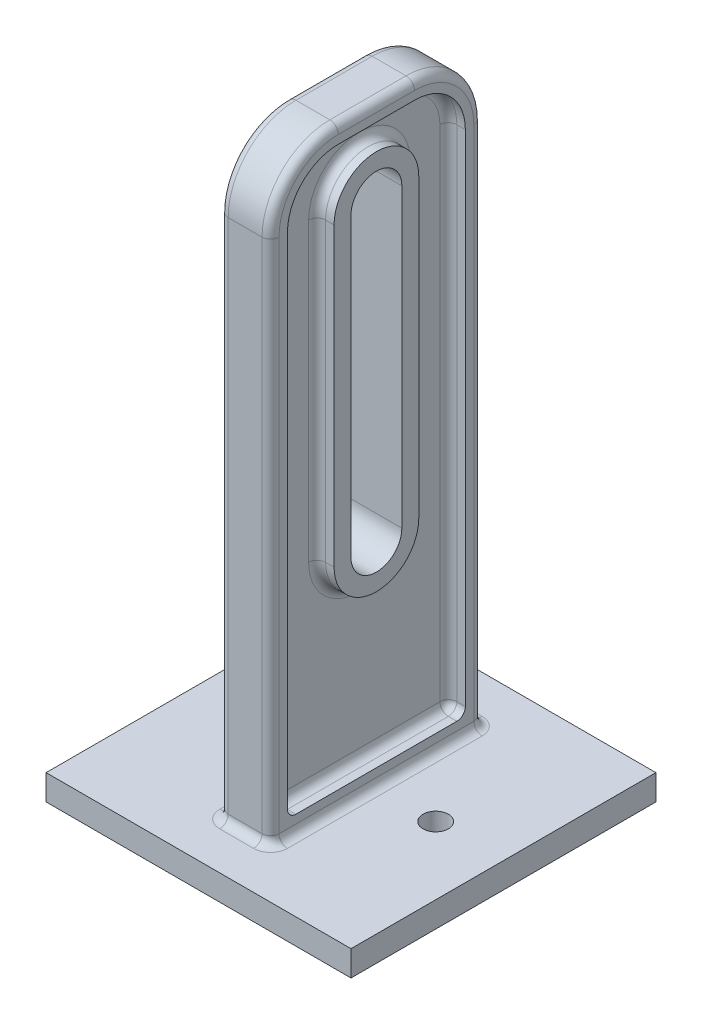
SolidWorks part; units mm, degrees
ref_plane "Front Plane" through (0, 0, 0) normal (0, 0, 1) x (1, 0, 0)
ref_plane "Top Plane" through (0, 0, 0) normal (0, 1, 0) x (1, 0, 0)
ref_plane "Right Plane" through (0, 0, 0) normal (1, 0, 0) x (0, 0, -1)
sketch "Sketch1" plane through (0, 0, 0) normal (0, 1, 0) x (1, 0, 0)
  line L1 (-18, -18) -> (18, -18)
  line L2 (-18, -18) -> (-18, 18)
  line L3 (-18, 18) -> (18, 18)
  line L4 (18, -18) -> (18, 18)
  line L5 (-18, -18) -> (18, 18) construction
  line L6 (-18, 18) -> (18, -18) construction
  point P0 (0, 0)
  dimension "D1" = 36
  dimension "D2" = 36
extrude "Boss-Extrude1" add sketch "Sketch1" along normal blind 3
sketch "Sketch2" plane through (0, 3, 0) normal (0, 1, 0) x (1, 0, 0)
  line L0 (0, 0) -> (0, 8.7395) construction
  line L1 (0, 0) -> (10, 0) construction
  circle A0 centre (-10, 0) radius 1.5
  circle A1 centre (10, 0) radius 1.5
  dimension "D2" = 3
  dimension "D1" = 20
extrude "Cut-Extrude1" cut sketch "Sketch2" against normal blind 3
sketch "Sketch3" plane through (0, 3, 0) normal (0, 1, 0) x (1, 0, 0)
  line L1 (-3, 12.5) -> (3, 12.5)
  line L2 (-3, 12.5) -> (-3, -12.5)
  line L3 (-3, -12.5) -> (3, -12.5)
  line L4 (3, 12.5) -> (3, -12.5)
  line L5 (-3, 12.5) -> (3, -12.5) construction
  line L6 (-3, -12.5) -> (3, 12.5) construction
  point P0 (0, 0)
  dimension "D1" = 25
  dimension "D2" = 6
extrude "Boss-Extrude2" add sketch "Sketch3" along normal blind 70
sketch "Sketch4" plane through (3, 0, 0) normal (1, 0, 0) x (0, 0, -1)
  line L0 (-12.5, 73) -> (12.5, 73) construction
  line L3 (-8.3079, 45.5) -> (10.2679, 45.5) construction
  line L4 (0, 0) -> (0, 52.2737) construction
  line L5 (0, 63) -> (0, 28) construction
  line L6 (3, 63) -> (3, 28)
  line L7 (-3, 63) -> (-3, 28)
  arc A2 (3, 63) -> (-3, 63) centre (0, 63) ccw
  arc A3 (-3, 28) -> (3, 28) centre (0, 28) ccw
  point P8 (0, 45.5)
  dimension "D2" = 3
  dimension "D3" = 35
  dimension "D1" = 10
extrude "Cut-Extrude2" cut sketch "Sketch4" against normal blind 70
fillet "Fillet1" radius 8 1 edges at (0, 73, 12.5)
fillet "Fillet2" radius 8 1 edges at (0, 73, -12.5)
sketch "Sketch5" plane through (3, 0, 0) normal (1, 0, 0) x (0, 0, -1)
  line L66 (-10.5, 5) -> (10.5, 5)
  line L67 (-10.5, 65) -> (-10.5, 5)
  line L68 (10.5, 5) -> (10.5, 65)
  line L69 (4.5, 71) -> (-4.5, 71)
  line L70 (-10.5, 5) -> (10.5, 5)
  line L71 (-10.5, 65) -> (-10.5, 5)
  line L72 (10.5, 5) -> (10.5, 65)
  line L73 (4.5, 71) -> (-4.5, 71)
  line L78 (5, 28) -> (5, 63)
  line L79 (-5, 63) -> (-5, 28)
  line L80 (5, 28) -> (5, 63)
  line L81 (-5, 63) -> (-5, 28)
  arc A44 (10.5, 65) -> (4.5, 71) centre (4.5, 65) ccw
  arc A45 (-4.5, 71) -> (-10.5, 65) centre (-4.5, 65) ccw
  arc A46 (10.5, 65) -> (4.5, 71) centre (4.5, 65) ccw
  arc A47 (-4.5, 71) -> (-10.5, 65) centre (-4.5, 65) ccw
  arc A52 (-5, 28) -> (5, 28) centre (0, 28) ccw
  arc A53 (5, 63) -> (-5, 63) centre (0, 63) ccw
  arc A54 (-5, 28) -> (5, 28) centre (0, 28) ccw
  arc A55 (5, 63) -> (-5, 63) centre (0, 63) ccw
  dimension "D1" = 2
  dimension "D2" = 2
extrude "Cut-Extrude3" cut sketch "Sketch5" against normal blind 2
mirror "Mirror1" about plane through (0, 0, 0) normal (1, 0, 0) of "Cut-Extrude3"
fillet "Fillet3" radius 1 4 edges at (1, 45.5, 5) (1, 68, 0) (1, 23, 0) (1, 45.5, -5)
fillet "Fillet4" radius 1 6 edges at (1, 69.2426, -8.7426) (1, 35, -10.5) (1, 5, 0) (1, 35, 10.5) (1, 71, 0) (1, 69.2426, 8.7426)
fillet "Fillet5" radius 1 2 edges at (2.5, 5, 10.5) (1.2929, 5.2929, 10.2071)
fillet "Fillet6" radius 1 2 edges at (2.5, 5, -10.5) (1.2929, 5.2929, -10.2071)
fillet "Fillet7" radius 1 4 edges at (-1, 45.5, 5) (-1, 23, 0) (-1, 68, 0) (-1, 45.5, -5)
fillet "Fillet8" radius 1 8 edges at (-2, 5, 10.5) (-2, 5, -10.5) (-1, 5, 0) (-1, 35, -10.5) (-1, 35, 10.5) (-1, 69.2426, -8.7426) (-1, 71, 0) (-1, 69.2426, 8.7426)
fillet "Fillet9" radius 1 14 edges at (3, 70.6569, 10.1569) (3, 73, 0) (3, 70.6569, -10.1569) (-3, 70.6569, 10.1569) (-3, 73, 0) (-3, 70.6569, -10.1569) (-3, 34, 12.5) (0, 3, 12.5) (3, 34, 12.5) (3, 3, 0) (3, 34, -12.5) (-3, 34, -12.5) (-3, 3, 0) (0, 3, -12.5)
